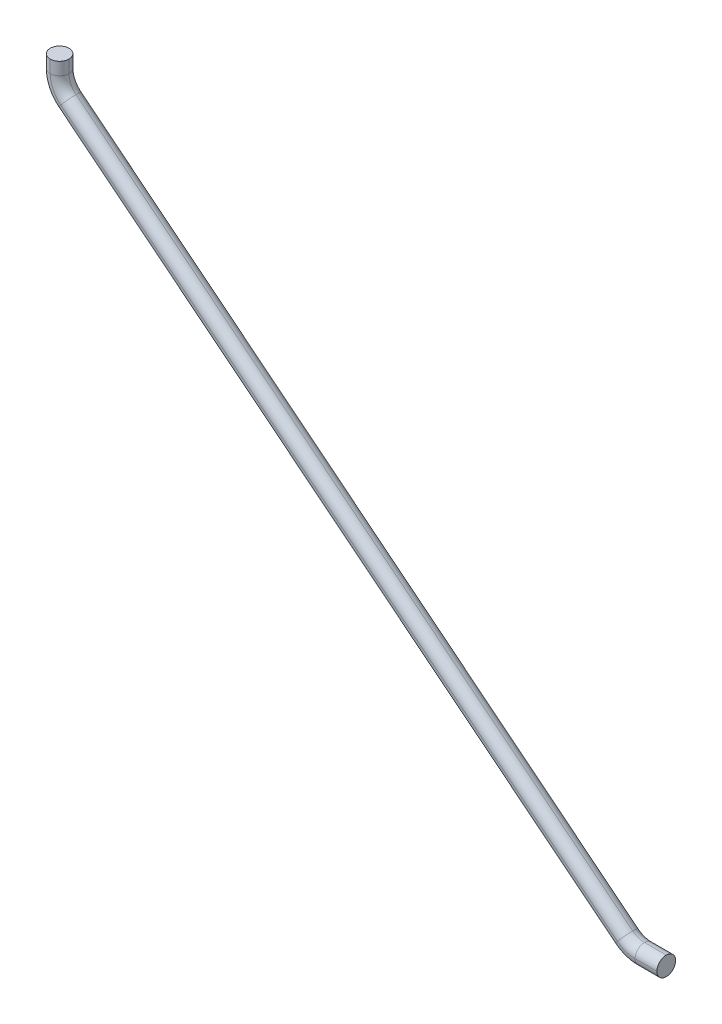
SolidWorks part; units mm, degrees
ref_plane "Front Plane" through (0, 0, 0) normal (0, 0, 1) x (1, 0, 0)
ref_plane "Top Plane" through (0, 0, 0) normal (0, 1, 0) x (1, 0, 0)
ref_plane "Right Plane" through (0, 0, 0) normal (1, 0, 0) x (0, 0, -1)
sketch "Sketch1" plane through (0, 0, 0) normal (0, 0, 1) x (1, 0, 0)
  line L0 (237.9269, -1499.5706) -> (237.9269, -1519.5706)
  line L5 (-418.536, -990.9457) -> (-418.536, -1004.3738)
  line L6 (-403.5426, -1035.5935) -> (189.7189, -1510.7903)
  line L7 (214.7256, -1519.5706) -> (237.9269, -1519.5706)
  line L8 (-398.536, -990.9457) -> (-398.536, -1004.3738)
  line L9 (-391.0393, -1019.9837) -> (202.2222, -1495.1805)
  line L10 (214.7256, -1499.5706) -> (237.9269, -1499.5706)
  line L11 (-398.536, -990.9457) -> (-418.536, -990.9457)
  arc A2 (-403.5426, -1035.5935) -> (-418.536, -1004.3738) centre (-378.536, -1004.3738) cw
  arc A3 (189.7189, -1510.7903) -> (214.7256, -1519.5706) centre (214.7256, -1479.5706) ccw
  arc A4 (-391.0393, -1019.9837) -> (-398.536, -1004.3738) centre (-378.536, -1004.3738) cw
  arc A5 (202.2222, -1495.1805) -> (214.7256, -1499.5706) centre (214.7256, -1479.5706) ccw
extrude "Boss-Extrude1" add sketch "Sketch1" along normal blind 10 and the other way blind 10
fillet "Fillet1" radius 10 20 edges at (226.3262, -1499.5706, -10) (208.0997, -1498.4412, -10) (-398.536, -997.6598, -10) (-396.5646, -1013.0322, -10) (-418.536, -997.6598, -10) (-414.5933, -1021.6905, -10) (226.3262, -1519.5706, -10) (201.4739, -1517.3118, -10) (226.3262, -1499.5706, 10) (208.0997, -1498.4412, 10) (-398.536, -997.6598, 10) (-396.5646, -1013.0322, 10) (-418.536, -997.6598, 10) (-414.5933, -1021.6905, 10) (226.3262, -1519.5706, 10) (201.4739, -1517.3118, 10) (-94.4085, -1257.5821, -10) (-106.9118, -1273.1919, -10) (-94.4085, -1257.5821, 10) (-106.9118, -1273.1919, 10)
